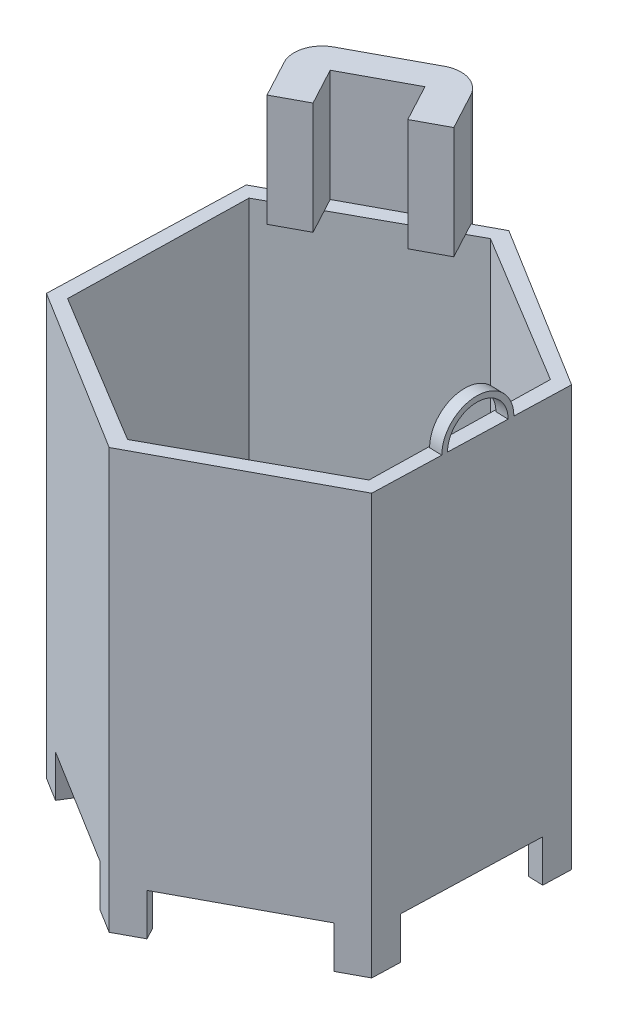
SolidWorks part; units mm, degrees
ref_plane "Front Plane" through (0, 0, 0) normal (0, 0, 1) x (1, 0, 0)
ref_plane "Top Plane" through (0, 0, 0) normal (0, 1, 0) x (1, 0, 0)
ref_plane "Right Plane" through (0, 0, 0) normal (1, 0, 0) x (0, 0, -1)
sketch "Sketch3" plane through (0, 0, 0) normal (0, 1, 0) x (1, 0, 0)
  line L1 (-26.2468, 20.0647) -> (-24.1003, 89.3135)
  line L2 (-24.1003, 89.3135) -> (-82.9982, 125.7968)
  line L3 (-82.9982, 125.7968) -> (-144.0427, 93.0313)
  line L4 (-144.0427, 93.0313) -> (-146.1892, 23.7826)
  line L5 (-146.1892, 23.7826) -> (-87.2913, -12.7008)
  line L6 (-87.2913, -12.7008) -> (-26.2468, 20.0647)
  line L7 (-30.8155, 23.6594) -> (-29.4978, 87.1543)
  line L8 (-29.4978, 87.1543) -> (-83.8271, 120.0429)
  line L9 (-83.8271, 120.0429) -> (-139.4741, 89.4366)
  line L10 (-139.4741, 89.4366) -> (-140.7918, 25.9417)
  line L11 (-140.7918, 25.9417) -> (-86.4625, -6.9468)
  line L12 (-86.4625, -6.9468) -> (-30.8155, 23.6594)
  circle A0 centre (-85.1448, 56.548) radius 60 construction
  circle A1 centre (-85.1448, 56.548) radius 55 construction
  dimension "D1" = 5.8133
extrude "body" add sketch "Sketch3" along normal blind 150
ref_plane "bot plane plane" through (0, 20, 0) normal (0, 1, 0) x (1, 0, 0)
sketch "Sketch7" plane through (0, 20, 0) normal (0, 1, 0) x (1, 0, 0)
  line L1 (-30.8155, 23.6594) -> (-29.4978, 87.1543)
  line L2 (-29.4978, 87.1543) -> (-83.8271, 120.0429)
  line L3 (-83.8271, 120.0429) -> (-139.4741, 89.4366)
  line L4 (-139.4741, 89.4366) -> (-140.7918, 25.9417)
  line L5 (-140.7918, 25.9417) -> (-86.4625, -6.9468)
  line L6 (-86.4625, -6.9468) -> (-30.8155, 23.6594)
  circle A0 centre (-85.1448, 56.548) radius 55 construction
  dimension "D1" = 0
extrude "bot plate" add sketch "Sketch7" along normal blind 10
ref_plane "Body plane 1" through (33.2995, 0, -53.7581) normal (0.5266, 0, -0.8501) x (-0.8501, 0, -0.5266)
sketch "Sketch8" plane through (33.2995, 0, -53.7581) normal (0.5266, 0, -0.8501) x (-0.8501, 0, -0.5266)
  line L0 (67.1489, 0) -> (-67.1489, 0) construction
  line L1 (77.5198, 15) -> (126.8019, 15)
  line L2 (77.5198, 15) -> (77.5198, 0)
  line L3 (77.5198, 0) -> (126.8019, 0)
  line L4 (126.8019, 15) -> (126.8019, 0)
  line L5 (67.5198, 150) -> (67.5198, 0) construction
  line L6 (136.8019, 150) -> (136.8019, 0) construction
  line L7 (67.1489, 20) -> (-67.1489, 20) construction
  dimension "D1" = 10
  dimension "D2" = 10
  dimension "D3" = 5
extrude "leg 1" cut sketch "Sketch8" against normal blind 122.0114
ref_plane "body plane 2" through (-26.843, 0, -0.8321) normal (0.9995, 0, 0.031) x (0.031, 0, -0.9995)
sketch "Sketch9" plane through (-26.843, 0, -0.8321) normal (0.9995, 0, 0.031) x (0.031, 0, -0.9995)
  line L0 (67.1489, 0) -> (-67.1489, 0) construction
  line L1 (29.2419, 15) -> (78.5239, 15)
  line L2 (29.2419, 15) -> (29.2419, 0)
  line L3 (29.2419, 0) -> (78.5239, 0)
  line L4 (78.5239, 15) -> (78.5239, 0)
  line L5 (19.2419, 150) -> (19.2419, 0) construction
  line L6 (88.5239, 150) -> (88.5239, 0) construction
  line L7 (67.1489, 20) -> (-67.1489, 20) construction
  dimension "D1" = 10
  dimension "D2" = 10
  dimension "D3" = 5
extrude "leg 2" cut sketch "Sketch9" against normal blind 125.3372
ref_plane "body plane 3" through (-70.9827, 0, -132.2461) normal (-0.4729, 0, -0.8811) x (-0.8811, 0, 0.4729)
sketch "Sketch10" plane through (-70.9827, 0, -132.2461) normal (-0.4729, 0, -0.8811) x (-0.8811, 0, 0.4729)
  line L0 (13.637, 0) -> (82.919, 0) construction
  line L1 (23.637, 15) -> (72.919, 15)
  line L2 (23.637, 15) -> (23.637, 0)
  line L3 (23.637, 0) -> (72.919, 0)
  line L4 (72.919, 15) -> (72.919, 0)
  line L5 (82.919, 150) -> (82.919, 0) construction
  line L6 (13.637, 150) -> (13.637, 0) construction
  line L7 (67.1489, 20) -> (-67.1489, 20) construction
  dimension "D1" = 10
  dimension "D2" = 10
  dimension "D3" = 5
extrude "leg 3" cut sketch "Sketch10" against normal blind 120.6092
hole_wizard "#9 (0.196) Diameter Hole1" positions "Sketch16" profile "Sketch17" hole size "#9" standard "ANSI Inch" end condition through all
sketch "Sketch16" plane through (0, 30, 0) normal (0, 1, 0) x (1, 0, 0)
  line L0 (-30.8155, 23.6594) -> (-29.4978, 87.1543) construction
  line L1 (-139.4741, 89.4366) -> (-140.7918, 25.9417) construction
  line L2 (-30.8155, 23.6594) -> (-29.4978, 87.1543) construction
  point P0 (-85.1449, 56.5429)
  point P6 (-85.6045, 88.3427)
  point P9 (-85.1449, 24.8032)
  point P13 (-112.6547, 56.356)
  point P18 (-57.6353, 56.7182)
  point P23 (-112.6547, 88.3427)
  point P25 (-112.6547, 24.8032)
  point P27 (-57.6353, 24.8032)
  point P29 (-57.6353, 88.3427)
  point P31 (-98.564, 72.6277)
  point P34 (-71.058, 72.6315)
  point P35 (-71.058, 40.6822)
  point P37 (-98.564, 40.6822)
  point P39 (-130.2291, 72.6277)
  point P41 (-130.2291, 40.6822)
  point P43 (-40.1781, 40.6822)
  point P45 (-40.1781, 72.6315)
  point P47 (-85.1449, 8.3563)
  point P49 (-85.6045, 106.0057)
  dimension "D1" = 55
  dimension "D2" = 63.5
  dimension "D3" = 31.75
  dimension "D4" = 31.75
  dimension "D5" = 27.5
  dimension "D6" = 27.5
  dimension "D7" = 41.25
  dimension "D8" = 41.25
sketch "Sketch17" plane through (-85.1449, 30, -56.5429) normal (1, 0, 0) x (0, 0, 1)
  line L0 (0, 0) -> (0, 30)
  line L1 (0, 30) -> (2.4892, 30)
  line L2 (2.4892, 30) -> (2.4892, 0)
  line L5 (2.4892, 0) -> (0, 0)
  line L11 (0, -6.35) -> (0, 107.95) construction
  dimension "Thru Hole Dia." = 4.9784
  dimension "Thru Hole Depth" = 30
sketch "Sketch18" plane through (-70.9827, 0, -132.2461) normal (-0.4729, 0, -0.8811) x (-0.8811, 0, 0.4729)
  line L0 (13.637, 150) -> (82.919, 150) construction
  line L1 (23.637, 150) -> (72.919, 150)
  line L2 (23.637, 150) -> (23.637, 135)
  line L3 (23.637, 135) -> (72.919, 135)
  line L4 (72.919, 150) -> (72.919, 135)
  line L6 (13.637, 150) -> (13.637, 0) construction
  line L7 (82.919, 150) -> (82.919, 0) construction
  dimension "D1" = 10
  dimension "D2" = 10
extrude "Boss-Extrude1" add sketch "Sketch18" along normal blind 10
ref_plane "sensor stand plane" through (0, 150, 0) normal (0, 1, 0) x (1, 0, 0)
sketch "Sketch21" plane through (0, 150, 0) normal (0, 1, 0) x (1, 0, 0)
  line L0 (-139.961, 106.5716) -> (-96.5385, 129.8785)
  line L1 (-139.961, 106.5716) -> (-135.2383, 97.7729)
  line L2 (-96.5385, 129.8785) -> (-91.8158, 121.0797)
  line L3 (-135.2383, 97.7729) -> (-91.8158, 121.0797)
extrude "Boss-Extrude2" add sketch "Sketch21" along normal blind 40
fillet "Fillet2" radius 10 1 edges at (-96.5385, 162.5, -129.8785)
fillet "Fillet3" radius 10 1 edges at (-139.961, 162.5, -106.5716)
fillet "Fillet4" radius 10 3 edges at (-97.734, 135, -125.9127) (-135.9951, 135, -105.3761) (-118.2498, 135, -118.2251)
ref_plane "sensor plane" through (-70.9893, 0, -132.2583) normal (0.4729, 0, 0.8811) x (0.8811, 0, -0.4729)
sketch "Sketch22" plane through (-70.9893, 0, -132.2583) normal (0.4729, 0, 0.8811) x (0.8811, 0, -0.4729)
  line L0 (67.1489, 150) -> (-67.1489, 150) construction
  line L1 (-72.919, 190) -> (-60.779, 190)
  line L2 (-72.919, 190) -> (-72.919, 150)
  line L3 (-72.919, 150) -> (-60.779, 150)
  line L4 (-60.779, 190) -> (-60.779, 150)
  line L6 (-23.637, 190) -> (-35.779, 190)
  line L7 (-23.637, 190) -> (-23.637, 150)
  line L8 (-23.637, 150) -> (-35.779, 150)
  line L9 (-35.779, 190) -> (-35.779, 150)
  dimension "D1" = 25
extrude "Boss-Extrude3" add sketch "Sketch22" along normal blind 15
sketch "Sketch23" plane through (-26.843, 0, -0.8321) normal (0.9995, 0, 0.031) x (0.031, 0, -0.9995)
  line L0 (67.1489, 150) -> (-67.1489, 150) construction
  line L1 (88.5239, 150) -> (88.5239, 0) construction
  circle A0 centre (56.0239, 150) radius 10.5
  circle A1 centre (56.0239, 150) radius 12.5
  dimension "D1" = 0
  dimension "D2" = 32.5
extrude "Boss-Extrude4" add sketch "Sketch23" against normal blind 4.5
